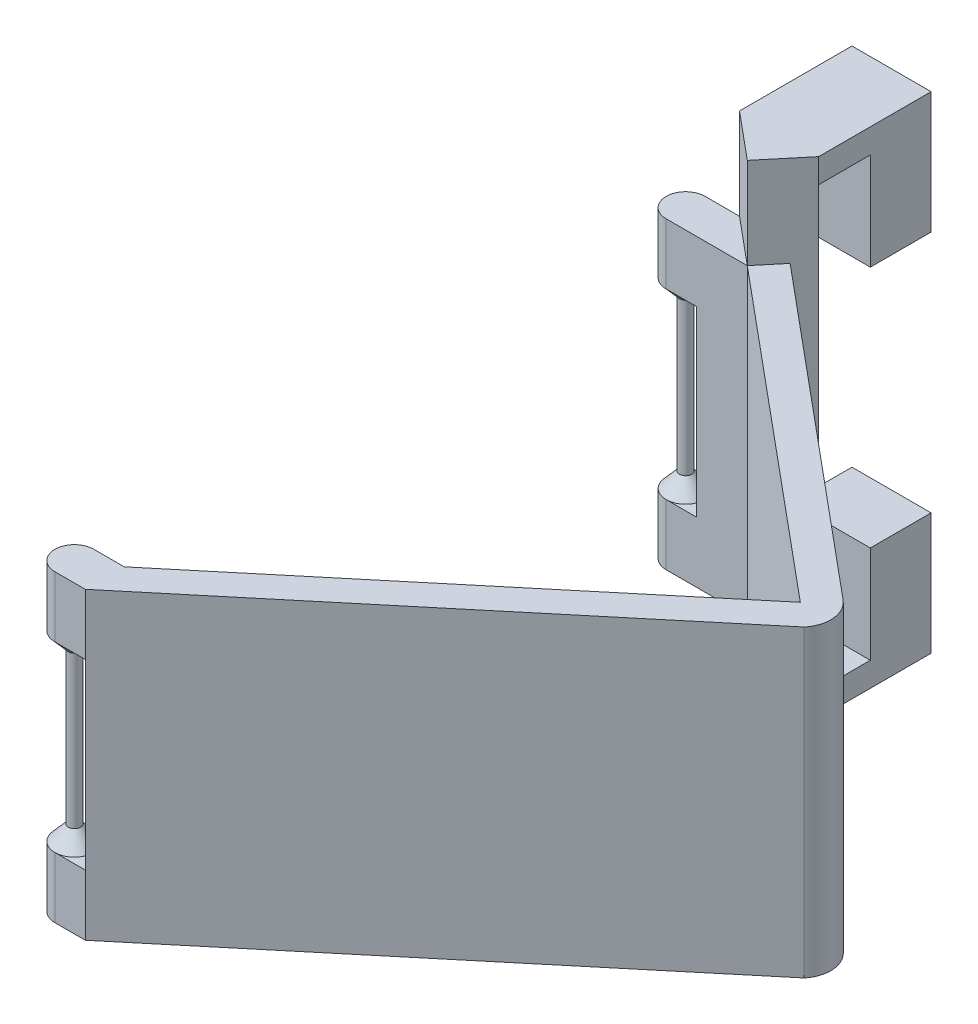
SolidWorks part; units mm, degrees
ref_plane "前视基准面" through (0, 0, 0) normal (0, 0, 1) x (1, 0, 0)
ref_plane "上视基准面" through (0, 0, 0) normal (0, 1, 0) x (1, 0, 0)
ref_plane "右视基准面" through (0, 0, 0) normal (1, 0, 0) x (0, 0, -1)
sketch "草图1" plane through (0, 0, 0) normal (0, 1, 0) x (1, 0, 0)
  line L0 (0, 0) -> (0, 50)
  line L1 (0, 0) -> (-0.664, -50.5533)
  line L2 (0, 0) -> (60, 0)
  line L3 (60, 0) -> (-0.664, -50.5533)
  line L4 (0, 50) -> (60, 0)
  line L5 (60, 0) -> (63.2009, 3.8411)
  line L6 (63.2009, 3.8411) -> (7.8102, 50)
  line L7 (60, 0) -> (63.8411, -3.2009)
  line L8 (63.8411, -3.2009) -> (7.6822, -50)
  line L9 (0, 50) -> (7.8102, 50)
  line L11 (7.6822, -50) -> (-0.664, -56.9551)
  line L12 (-0.664, -56.9551) -> (-0.664, -50.5533)
  arc A0 (63.2009, 3.8411) -> (63.8411, -3.2009) centre (60, 0) cw
extrude "凸台-拉伸1" add sketch "草图1" along normal blind 50 contours L3 L8 L7 | A0 L5 L7 | L9 L4 L5 L6 region at (32.7161, 0, -25.9475) region at (30.6381, 0, 27.7019) region at (62.9887, 0, -0.2717)
sketch "草图3" plane through (27.7911, 0, -33.3493) normal (0.6402, 0, -0.7682) x (-0.7682, 0, -0.6402)
  line L0 (-46.0933, 25) -> (26.0092, 25) construction
  line L1 (-46.0933, 50) -> (-46.0933, 0) construction
  line L2 (26.0092, 50) -> (26.0092, 0) construction
ref_plane "基准面1" through (0, 25, 0) normal (0, -1, 0) x (-0.7682, 0, -0.6402)
sketch "草图4" plane through (0, 50, 0) normal (0, 1, 0) x (1, 0, 0)
  line L0 (0, 50) -> (7.6822, 43.5982)
  line L1 (0, 50) -> (60, 0) construction
  line L2 (7.6822, 43.5982) -> (10.8831, 47.4393)
  line L3 (63.2009, 3.8411) -> (7.8102, 50) construction
  line L4 (10.8831, 47.4393) -> (7.8102, 50)
  line L5 (7.8102, 50) -> (0, 50)
  line L6 (7.8102, 50) -> (19.6167, 50)
  line L7 (10.8831, 47.4393) -> (13.0171, 50)
  line M4 (63.2009, 3.8411) -> (7.8102, 50)
  line M5 (7.8102, 50) -> (0, 50)
  line M6 (0, 50) -> (60, 0)
extrude "凸台-拉伸3" add sketch "草图4" along normal blind 15 and the other way blind 50 contours L2 M6 M4 M5 | L7 L6 M4 region at (6.2006, 50, -47.6222) region at (10.5702, 50, -49.1464)
sketch "草图5" plane through (0, 0, -50) normal (0, 0, -1) x (-1, 0, 0)
  line L0 (-13.0171, 65) -> (-13.0171, 61)
  line L1 (-13.0171, 0) -> (-13.0171, 65) construction
  line L2 (-13.0171, 61) -> (0, 61)
  line L3 (0, 65) -> (0, 0) construction
  line L4 (0, 61) -> (0, 65)
  line L5 (0, 65) -> (-13.0171, 65)
extrude "凸台-拉伸4" add sketch "草图5" along normal blind 18.5
sketch "草图6" plane through (0, 61, 0) normal (0, -1, 0) x (1, 0, 0)
  line L0 (0, -68.5) -> (0, -58.5)
  line L1 (0, -68.5) -> (0, -50) construction
  line L2 (13.0171, -68.5) -> (0, -68.5) construction
  line L3 (0, -58.5) -> (13.0171, -58.5)
  line L4 (13.0171, -68.5) -> (13.0171, -50) construction
  line L5 (13.0171, -58.5) -> (13.0171, -68.5)
  line L6 (13.0171, -68.5) -> (0, -68.5)
extrude "凸台-拉伸5" add sketch "草图6" along normal blind 16
mirror "镜向4" about plane through (0, 25, 0) normal (0, -1, 0) of "凸台-拉伸5", "凸台-拉伸3", "凸台-拉伸4"
sketch "草图7" plane through (0, 50, 0) normal (0, 1, 0) x (1, 0, 0)
  line L0 (-0.664, -53.7542) -> (-5.664, -53.7542)
  line L1 (-0.664, -56.9551) -> (-0.664, -50.5533) construction
  line L2 (-5.664, -53.7542) -> (-5.664, 89.3377)
sketch "草图8" plane through (0, 50, 0) normal (0, 1, 0) x (1, 0, 0)
  line L0 (-0.664, -50.5533) -> (-0.664, 65.3859)
  line L1 (7.6822, 43.5982) -> (-0.664, 43.5982)
  line L2 (-0.664, 43.5982) -> (-0.664, 50)
  line L3 (-0.664, 50) -> (0, 50)
  line L4 (0, 50) -> (7.6822, 43.5982)
extrude "凸台-拉伸6" add sketch "草图8" against normal blind 50 contours L1 L2 L3 L4
sketch "草图9" plane through (0, 0, 0) normal (0, -1, 0) x (1, 0, 0)
  line L0 (-0.664, 56.9551) -> (-5.664, 56.9551)
  line L1 (-0.664, 50.5533) -> (-5.664, 50.5533)
  line L2 (-5.664, 53.7542) -> (-5.664, -89.3377) construction
  line L3 (-0.664, 56.9551) -> (-0.664, 50.5533)
  line L4 (-5.664, 56.9551) -> (-5.664, 50.5533)
  arc A0 (-5.664, 56.9551) -> (-5.664, 50.5533) centre (-5.664, 53.7542) ccw
  line M5 (-0.664, 56.9551) -> (-0.664, 50.5533)
extrude "凸台-拉伸7" add sketch "草图9" against normal blind 10 contours L0 L4 L1 M5 | L4 A0 region at (-3.164, 0, 53.7542) region at (-7.0225, 0, 53.7542)
sketch "草图10" plane through (0, 0, 0) normal (0, -1, 0) x (1, 0, 0)
  line L0 (-0.664, -43.5982) -> (-5.664, -43.5982)
  line L1 (-5.664, 53.7542) -> (-5.664, -89.3377) construction
  line L2 (-0.664, -50) -> (-5.664, -50)
  line L3 (-5.664, -43.5982) -> (-5.664, -50)
  arc A0 (-5.664, -43.5982) -> (-5.664, -50) centre (-5.664, -46.7991) ccw
  line M3 (-0.664, -43.5982) -> (-0.664, -50)
extrude "凸台-拉伸8" add sketch "草图10" against normal blind 10 contours L0 L3 L2 M3 | L3 A0 region at (-3.164, 0, -46.7991) region at (-7.0225, 0, -46.7991)
mirror "镜向5" about plane through (0, 25, 0) normal (0, -1, 0) of "凸台-拉伸8", "凸台-拉伸7"
sketch "草图11" plane through (0, 40, 0) normal (0, -1, 0) x (1, 0, 0)
  circle A0 centre (-5.664, 53.7542) radius 1
extrude "凸台-拉伸9" add sketch "草图11" along normal blind 30
ref_plane "基准面3" through (0, 0, 53.7542) normal (0, 0, -1) x (-1, 0, 0)
sketch "草图14" plane through (0, 0, 53.7542) normal (0, 0, -1) x (-1, 0, 0)
  line L5 (6.664, 10) -> (8.8649, 10)
  line L6 (6.664, 10) -> (6.664, 12.5)
  line L7 (6.664, 10) -> (6.664, 40) construction
  line L8 (6.664, 12.5) -> (8.8649, 10)
ref_axis "基准轴2" through (-5.664, 10, 53.7542) along (0, 1, 0)
revolve "旋转1" add sketch "草图14" angle 360 about axis through (-5.664, 10, 53.7542) along (0, 1, 0) region at (-7.3976, 10.8333, 53.7542)
mirror "镜向6" about plane through (0, 25, 0) normal (0, -1, 0) of "旋转1"
sketch "草图15" plane through (0, 10, 0) normal (0, 1, 0) x (1, 0, 0)
  circle A0 centre (-5.664, 46.7991) radius 1
extrude "凸台-拉伸10" add sketch "草图15" along normal blind 30
sketch "草图16" plane through (0, 0, 0) normal (0, -1, 0) x (1, 0, 0)
  line L0 (-5.664, -46.7991) -> (2.4555, -46.7991)
ref_plane "基准面4" through (0, 0, -46.7991) normal (0, 0, 1) x (1, 0, 0)
ref_axis "基准轴3" through (-5.664, 40, -46.7991) along (0, -1, 0)
sketch "草图17" plane through (0, 0, -46.7991) normal (0, 0, 1) x (1, 0, 0)
  line L0 (-6.664, 10) -> (-6.664, 12.5)
  line L1 (-5.664, 10) -> (-8.8649, 10) construction
  line L2 (-6.664, 12.5) -> (-8.8649, 10)
  line L3 (-8.8649, 10) -> (-6.664, 10)
revolve "旋转2" add sketch "草图17" angle 360 about axis through (-5.664, 40, -46.7991) along (0, -1, 0)
mirror "镜向7" about plane through (0, 25, 0) normal (0, -1, 0) of "旋转2"
